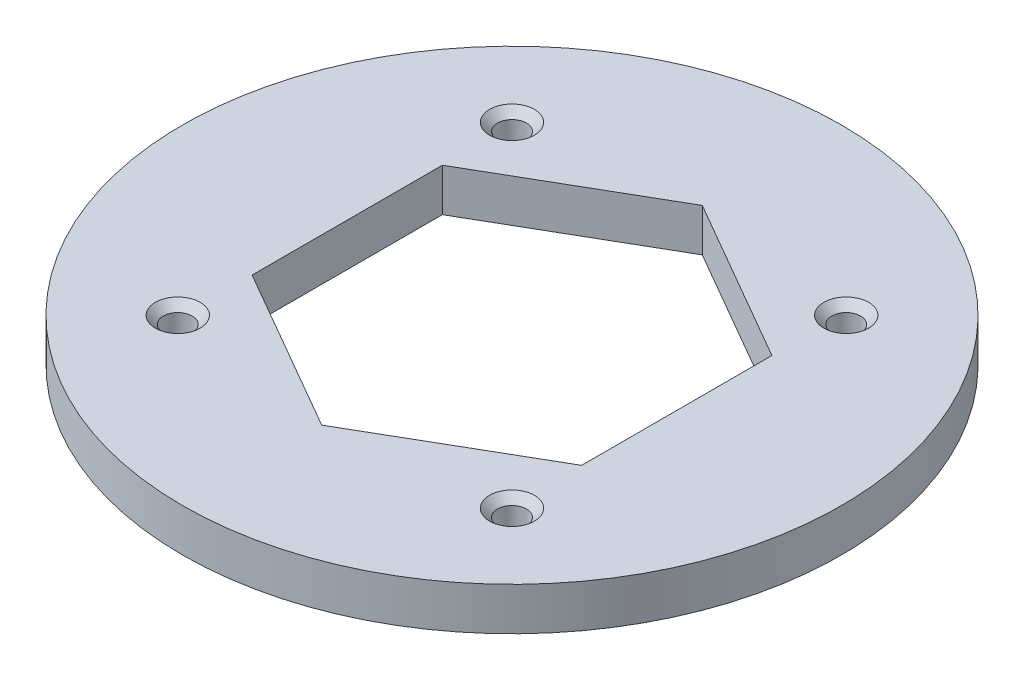
SolidWorks part; units mm, degrees
ref_plane "Front Plane" through (0, 0, 0) normal (0, 0, 1) x (1, 0, 0)
ref_plane "Top Plane" through (0, 0, 0) normal (0, 1, 0) x (1, 0, 0)
ref_plane "Right Plane" through (0, 0, 0) normal (1, 0, 0) x (0, 0, -1)
sketch "Sketch1" plane through (0, 0, 0) normal (0, 1, 0) x (1, 0, 0)
  line L0 (-25.3553, -25.3553) -> (-25.3553, 25.3553) construction
  line L1 (-35.3553, -35.3553) -> (35.3553, -35.3553) construction
  line L2 (-35.3553, -35.3553) -> (-35.3553, 35.3553) construction
  line L3 (-35.3553, 35.3553) -> (35.3553, 35.3553) construction
  line L4 (35.3553, -35.3553) -> (35.3553, 35.3553) construction
  line L5 (-35.3553, -35.3553) -> (35.3553, 35.3553) construction
  line L6 (-35.3553, 35.3553) -> (35.3553, -35.3553) construction
  line L7 (-25.3553, 25.3553) -> (25.3553, 25.3553) construction
  line L8 (25.3553, -25.3553) -> (25.3553, 25.3553) construction
  line L9 (-25.3553, -25.3553) -> (25.3553, -25.3553) construction
  line L10 (0, -55) -> (0, 55) construction
  line L11 (-55, 0) -> (55, 0) construction
  circle A0 centre (0, 0) radius 50
  circle A1 centre (-25.3553, 25.3553) radius 2.2
  circle A3 centre (25.3553, 25.3553) radius 2.2
  circle A6 centre (-25.3553, -25.3553) radius 2.2
  circle A7 centre (25.3553, -25.3553) radius 2.2
  dimension "D1" = 100
  dimension "D4" = 4.4
  dimension "D2" = 10
extrude "Boss-Extrude1" add sketch "Sketch1" along normal blind 6.5 contours A0 region at (0, 0, 0)
extrude "Boss-Extrude2" add sketch "Sketch1<3>" along normal blind 2 contours A7 | A3 | A1 | A6 region at (0, 0, 0)
sketch "Sketch1<3>" plane through (0, 0, 0) normal (0, 1, 0) x (1, 0, 0) same geometry as "Sketch1"
sketch "Sketch2" plane through (0, 0, 0) normal (0, -1, 0) x (1, 0, 0)
  line L1 (-35.3553, -35.3553) -> (35.3553, -35.3553) construction
  line L2 (-35.3553, -35.3553) -> (-35.3553, 35.3553) construction
  line L3 (-35.3553, 35.3553) -> (35.3553, 35.3553) construction
  line L4 (35.3553, -35.3553) -> (35.3553, 35.3553) construction
  line L5 (-35.3553, -35.3553) -> (35.3553, 35.3553) construction
  line L6 (-35.3553, 35.3553) -> (35.3553, -35.3553) construction
  circle A0 centre (0, 0) radius 50 construction
  circle A1 centre (0, 35.3553) radius 5.5
  point P0 (0, 0)
extrude "Cut-Extrude1" cut sketch "Sketch2" against normal blind 2.5
sketch "Sketch3" plane through (0, 6.5, 0) normal (0, 1, 0) x (1, 0, 0)
  line L1 (0, 28.8675) -> (-25, 14.4338)
  line L2 (-25, 14.4338) -> (-25, -14.4338)
  line L3 (-25, -14.4338) -> (0, -28.8675)
  line L4 (0, -28.8675) -> (25, -14.4338)
  line L5 (25, -14.4338) -> (25, 14.4338)
  line L6 (25, 14.4338) -> (0, 28.8675)
  circle A0 centre (0, 0) radius 25 construction
  dimension "D1" = 50
extrude "Cut-Extrude2" cut sketch "Sketch3" against normal blind 10
chamfer "Chamfer1" distance 1.2 angle 45 4 edges at (25.3553, 6.5, -23.1553) (-25.3553, 6.5, -23.1553) (-25.3553, 6.5, 27.5553) (25.3553, 6.5, 27.5553)
